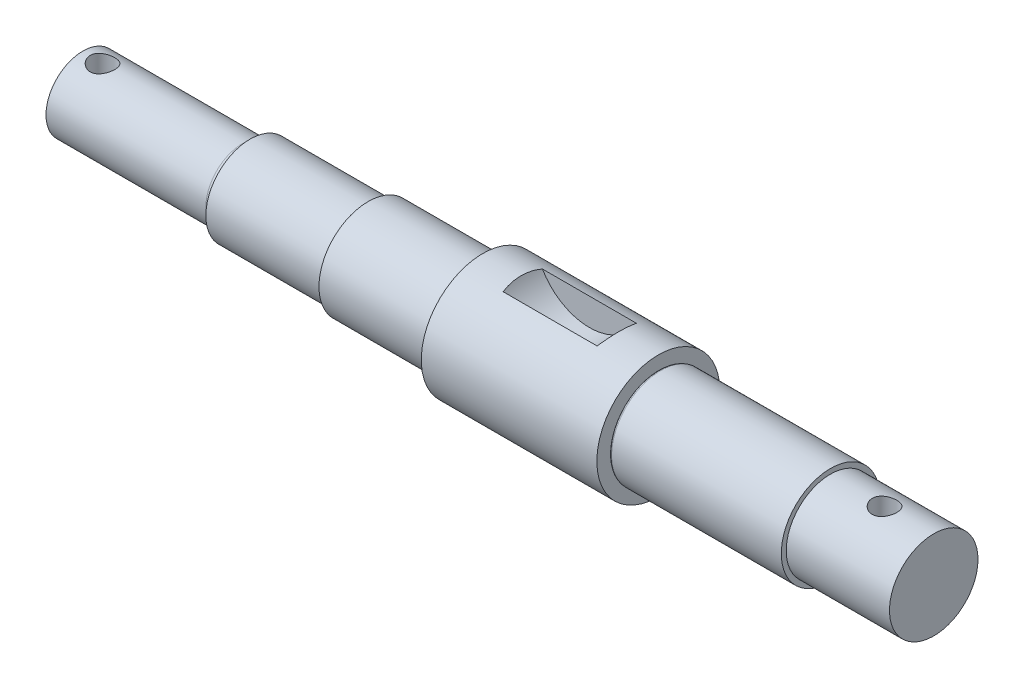
SolidWorks part; units mm, degrees
ref_plane "정면" through (0, 0, 0) normal (0, 0, 1) x (1, 0, 0)
ref_plane "윗면" through (0, 0, 0) normal (0, 1, 0) x (1, 0, 0)
ref_plane "우측면" through (0, 0, 0) normal (1, 0, 0) x (0, 0, -1)
sketch "스케치2" plane through (0, 0, 0) normal (1, 0, 0) x (0, 0, -1)
  circle A0 centre (0, 0) radius 9
  circle A1 centre (0, 0) radius 10
  circle A2 centre (0, 0) radius 12.5
extrude "보스-돌출1" add sketch "스케치2" along normal blind 21 contours A0
extrude "보스-돌출2" add sketch "스케치2<3>" against normal blind 35 contours A1
sketch "스케치2<3>" plane through (0, 0, 0) normal (1, 0, 0) x (0, 0, -1) same geometry as "스케치2"
extrude "보스-돌출3" add sketch "스케치2<4>" against normal blind 35.7 from offset 35 separate body contours A2 offset against normal yes
sketch "스케치2<4>" plane through (0, 0, 0) normal (1, 0, 0) x (0, 0, -1) same geometry as "스케치2"
sketch "스케치3" plane through (-70.7, 0, 0) normal (-1, 0, 0) x (0, 0, 1)
  circle A0 centre (0, 0) radius 10
  circle A1 centre (0, 0) radius 9
  circle A2 centre (0, 0) radius 7.5
extrude "보스-돌출4" add sketch "스케치3" along normal blind 23.3 contours A0
extrude "보스-돌출5" add sketch "스케치3<3>" along normal blind 34 from offset 13.3 contours A1
sketch "스케치3<3>" plane through (-70.7, 0, 0) normal (-1, 0, 0) x (0, 0, 1) same geometry as "스케치3"
extrude "보스-돌출6" add sketch "스케치3<4>" along normal blind 34 and the other way blind 16 from offset 47.3 contours A2
sketch "스케치3<4>" plane through (-70.7, 0, 0) normal (-1, 0, 0) x (0, 0, 1) same geometry as "스케치3"
fillet "필렛1" radius 1.5 1 edges at (-118, 0, 7.5)
fillet "필렛2" radius 0.5 1 edges at (-70.7, 0, 10)
fillet "필렛3" radius 0.5 1 edges at (-35, 0, -10)
ref_plane "평면1" through (0, 14, 0) normal (0, 1, 0) x (1, 0, 0)
sketch "스케치4" plane through (0, 14, 0) normal (0, 1, 0) x (1, 0, 0)
  line L0 (21, -9) -> (21, 9) construction
  line L1 (-152, 7.5) -> (-152, -7.5) construction
  circle A0 centre (11, 0) radius 2.5
  circle A1 centre (-148, 0) radius 2.5
  dimension "D1" = 5
  dimension "D3" = 5
  dimension "D2" = 10
  dimension "D4" = 4
extrude "컷-돌출1" cut sketch "스케치4" against normal blind 34 contours A1 | A0 region at (11, 14, 0) region at (-148, 14, 0)
sketch "스케치5" plane through (0, 0, 0) normal (0, 0, 1) x (1, 0, 0)
  line L0 (0, 0) -> (-170.9543, 0) construction
  line L1 (-35, -12.5) -> (-35, 12.5) construction
  circle A0 centre (-53, 17.3) radius 11
  dimension "D1" = 17.3
  dimension "D2" = 18
extrude "컷-돌출2" cut sketch "스케치5" against normal blind 4 and the other way blind 4
